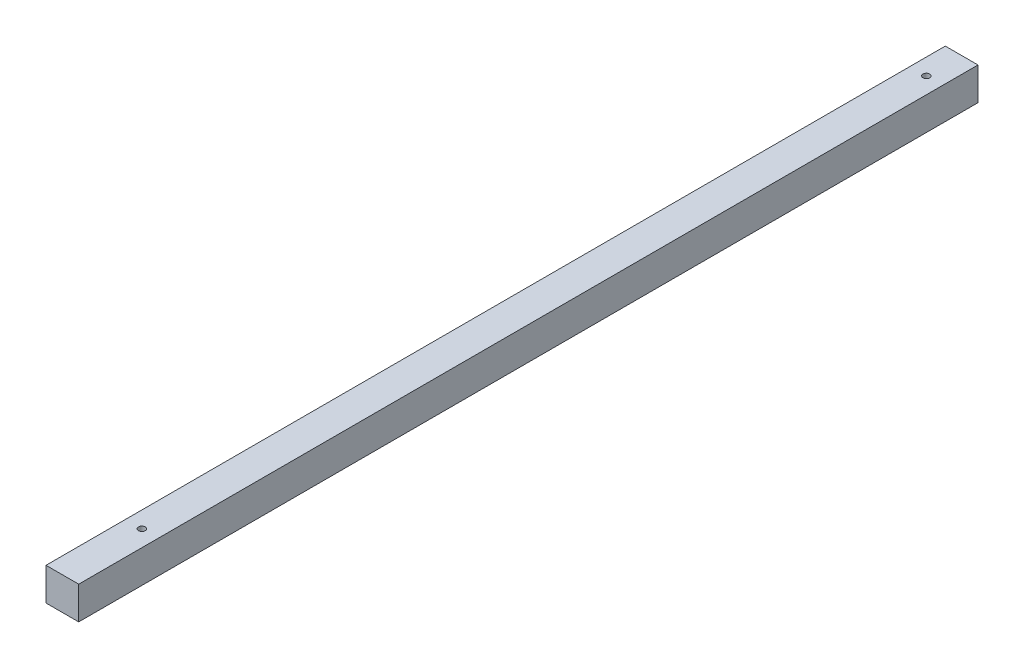
SolidWorks part; units mm, degrees
ref_plane "Plan de face" through (0, 0, 0) normal (0, 0, 1) x (1, 0, 0)
ref_plane "Plan de dessus" through (0, 0, 0) normal (0, 1, 0) x (1, 0, 0)
ref_plane "Plan de droite" through (0, 0, 0) normal (1, 0, 0) x (0, 0, -1)
sketch "Esquisse1" plane through (0, 0, 0) normal (0, 0, 1) x (1, 0, 0)
  line L1 (0, 0) -> (10, 0)
  line L2 (0, 0) -> (0, 10)
  line L3 (0, 10) -> (10, 10)
  line L4 (10, 0) -> (10, 10)
  dimension "D1" = 10
  dimension "D2" = 10
extrude "Boss.-Extru.1" add sketch "Esquisse1" along normal blind 275
sketch "Esquisse2" plane through (0, 10, 0) normal (0, 1, 0) x (1, 0, 0)
  line L0 (10, 0) -> (0, 0) construction
  line L1 (10, -275) -> (10, 0) construction
  circle A0 centre (5, -10.81) radius 1.025
  dimension "D1" = 2.05
  dimension "D2" = 10.81
  dimension "D3" = 5
extrude "Enlèv. mat.-Extru.1" cut sketch "Esquisse2" against normal through all contours A0
sketch "Esquisse3" plane through (0, 10, 0) normal (0, 1, 0) x (1, 0, 0)
  line L0 (10, -275) -> (0, -275) construction
  line L1 (0, -275) -> (0, 0) construction
  circle A0 centre (5, -250.68) radius 1.025
  dimension "D1" = 24.32
  dimension "D2" = 5
  dimension "D3" = 2.05
extrude "Enlèv. mat.-Extru.2" cut sketch "Esquisse3" against normal through all
